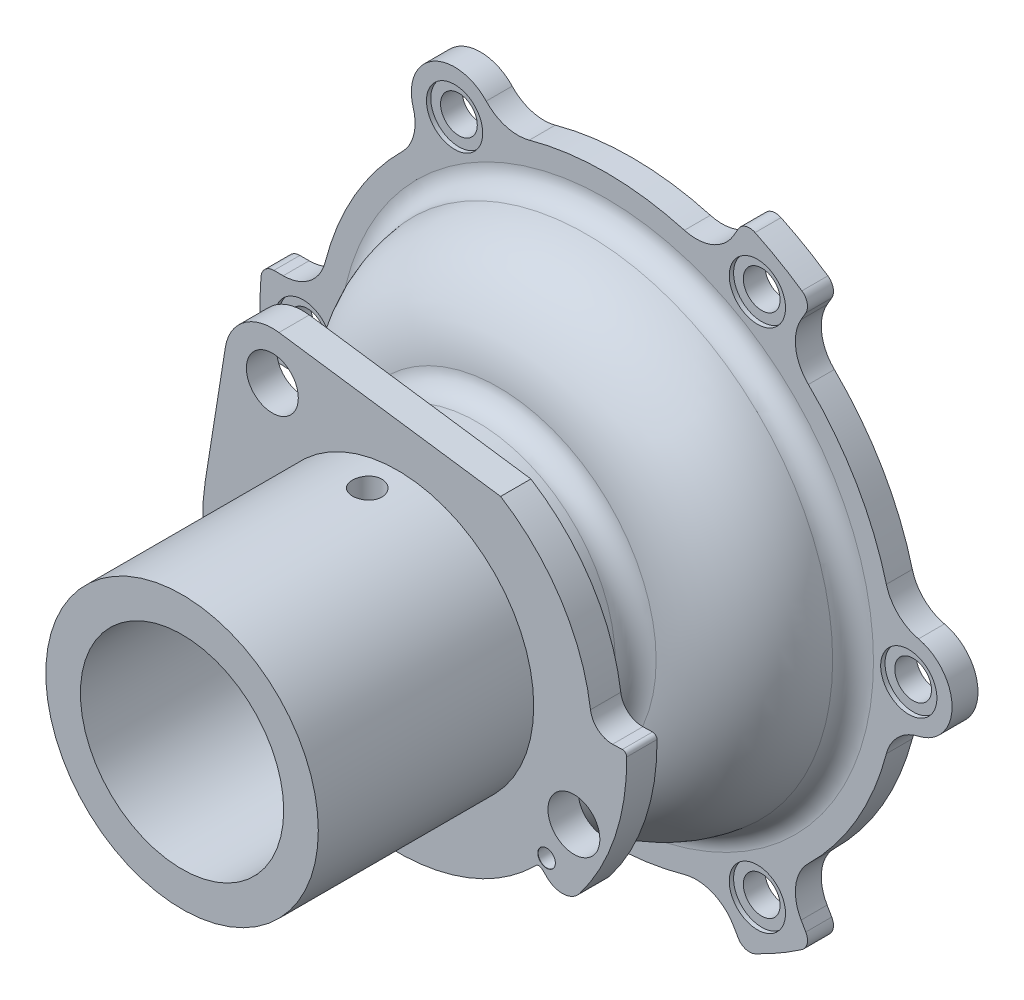
SolidWorks part; units mm, degrees
ref_plane "前视基准面" through (0, 0, 0) normal (0, 0, 1) x (1, 0, 0)
ref_plane "上视基准面" through (0, 0, 0) normal (0, 1, 0) x (1, 0, 0)
ref_plane "右视基准面" through (0, 0, 0) normal (1, 0, 0) x (0, 0, -1)
sketch "草图5" plane through (0, 0, 0) normal (0, 0, 1) x (1, 0, 0)
  circle A0 centre (0, 0) radius 67
  dimension "D1" = 134
extrude "凸台-拉伸1" add sketch "草图5" along normal blind 6
sketch "草图6" plane through (0, 0, 0) normal (0, 0, 1) x (1, 0, 0)
  circle A0 centre (0, 0) radius 31.5
  dimension "D1" = 63
extrude "凸台-拉伸2" add sketch "草图6" along normal blind 104
sketch "草图7" plane through (0, 0, 0) normal (0, 0, 1) x (1, 0, 0)
  line L0 (0, 0) -> (-41.4994, 49.457) construction
  line L1 (0, -57.2) -> (0, 57.2) construction
  line L2 (-39.7878, 36.2068) -> (-44.4369, 7.0969)
  line L3 (-27.3945, 45.3649) -> (23.8436, 38.1639)
  line L4 (34.6624, -32.8255) -> (33.392, -31.6224)
  line L5 (51.9667, 1.57) -> (49.7267, 1.5023)
  line L6 (-8.5155, -48.7492) -> (-6.1102, -44.5832)
  line L7 (57.2, 0) -> (-57.2, 0) construction
  line L8 (0, 0) -> (-47.6758, -82.5768) construction
  line L9 (-34.9226, -34.4878) -> (-32.799, -30.8095)
  arc A0 (-44.4369, 7.0969) -> (-32.799, -30.8095) centre (0, 0) ccw
  arc A1 (-27.3945, 45.3649) -> (-39.7878, 36.2068) centre (-28.9254, 34.472) ccw
  arc A2 (52.9968, 0.5814) -> (42.0693, -32.2363) centre (0, 0) cw
  arc A3 (44.6181, 5.85) -> (23.8436, 38.1639) centre (0, 0) ccw
  arc A4 (49.7267, 1.5023) -> (44.6181, 5.85) centre (49.5757, 6.5) cw
  arc A5 (52.9968, 0.5814) -> (51.9667, 1.57) centre (51.9969, 0.5704) ccw
  arc A6 (42.0693, -32.2363) -> (34.6624, -32.8255) centre (38.1005, -29.1951) cw
  arc A7 (33.392, -31.6224) -> (31.9934, -31.6452) centre (32.7044, -32.3485) ccw
  arc A8 (-33.7792, -40.8407) -> (-14.1837, -51.0669) centre (0, 0) ccw
  arc A9 (-6.1102, -44.5832) -> (31.9934, -31.6452) centre (0, 0) ccw
  arc A10 (-33.7792, -40.8407) -> (-34.9226, -34.4878) centre (-30.5925, -36.9878) cw
  arc A11 (-14.1837, -51.0669) -> (-8.5155, -48.7492) centre (-12.8456, -46.2492) ccw
  point P16 (44.9795, 1.3589)
  dimension "D1" = 90
  dimension "D3" = 22
  dimension "D5" = 5
  dimension "D6" = 1
  dimension "D8" = 5
  dimension "D9" = 1
  dimension "D10" = 53
  dimension "D14" = 53
  dimension "D15" = 5
  dimension "D2" = 40
  dimension "D4" = 42
  dimension "D7" = 1.5
  dimension "D11" = 30
  dimension "D12" = 17
  dimension "D13" = 13
extrude "凸台-拉伸3" add sketch "草图7" against normal blind 7 from offset 54.2
sketch "草图9" plane through (0, 0, 0) normal (0, 0, 1) x (1, 0, 0)
  circle A0 centre (0, 0) radius 32
  dimension "D1" = 64
extrude "凸台-拉伸5" add sketch "草图9" along normal up to surface (47.2 mm away) up to face at (31.5, 0, 47.2)
sketch "草图11" plane through (0, 0, 54.2) normal (0, 0, 1) x (1, 0, 0)
  line L0 (40.7839, -19.0178) -> (0, 0) construction
  line L1 (57.2, 0) -> (-57.2, 0) construction
  line L2 (-19.0178, -40.7839) -> (0, 0) construction
  line L3 (0, -57.2) -> (0, 57.2) construction
  circle A0 centre (-28.9254, 34.472) radius 6
  arc A1 (-27.3945, 45.3649) -> (-39.7878, 36.2068) centre (-28.9254, 34.472) ccw construction
  circle A2 centre (40.7839, -19.0178) radius 6
  arc A3 (44.6181, 5.85) -> (23.8436, 38.1639) centre (0, 0) ccw construction
  circle A4 centre (-19.0178, -40.7839) radius 6
  arc A6 (-6.1102, -44.5832) -> (31.9934, -31.6452) centre (0, 0) ccw construction
  dimension "D1" = 12
  dimension "D2" = 12
  dimension "D4" = 12
  dimension "D3" = 25
  dimension "D5" = 25
extrude "切除-拉伸1" cut sketch "草图11" against normal blind 7
sketch "草图12" plane through (0, 0, 54.2) normal (0, 0, 1) x (1, 0, 0)
  line L0 (0, 0) -> (34.472, -28.9254) construction
  line L1 (0, 0) -> (-29.5781, -36.5259) construction
  line L2 (57.2, 0) -> (-57.2, 0) construction
  line L3 (0, -57.2) -> (0, 57.2) construction
  arc A0 (-6.1102, -44.5832) -> (31.9934, -31.6452) centre (0, 0) ccw construction
  point P11 (34.472, -28.9254)
  point P13 (-29.5781, -36.5259)
  dimension "D1" = 40
  dimension "D2" = 39
  dimension "D3" = 47
hole_wizard "Ø4.0mm 暗销孔1" positions "草图14" profile "草图13" hole size "Ø4.0" standard "GB"
sketch "草图14" plane through (0, 0, 54.2) normal (0, 0, 1) x (1, 0, 0)
  point P0 (21.1612, -36.8231)
  point P1 (34.472, -28.9254)
  point P4 (-29.5781, -36.5259)
sketch "草图13" plane through (-29.5781, -36.5259, 54.2) normal (1, 0, 0) x (0, -1, 0)
  line L0 (0, 0) -> (0, 7)
  line L1 (0, 7) -> (2, 7)
  line L2 (2, 7) -> (2, 0.0433)
  line L3 (2, 0.0433) -> (2.025, 0)
  line L5 (2.025, 0) -> (0, 0)
  line L6 (-2, 0.0433) -> (-2.025, 0) construction
  line L11 (0, -6.35) -> (0, 107.95) construction
  dimension "通孔孔直径" = 4
  dimension "通孔孔深度" = 7
  dimension "近端锥形沉头孔直径" = 4.05
  dimension "近端锥形沉头孔角度" = 60
sketch "草图15" plane through (0, 0, 0) normal (0, 1, 0) x (1, 0, 0)
  line L0 (0, 0) -> (0, -139.9578) construction
  line L1 (-73.7, 0) -> (73.7, 0) construction
  line L2 (-67, -6) -> (67, -6) construction
  line L3 (11.0871, -6) -> (56.9129, -6)
  arc A0 (11.0871, -6) -> (56.9129, -6) centre (34, -8) ccw
  point P7 (34, -31)
  dimension "D1" = 46
  dimension "D2" = 8
  dimension "D3" = 68
revolve "旋转1" add sketch "草图15" angle 360 about L0
fillet "圆角1" radius 5 1 edges at (-56.9129, 0, 6)
fillet "圆角2" radius 5 1 edges at (-32, 0, 30.9129)
sketch "草图17" plane through (0, 0, 0) normal (0, 0, 1) x (1, 0, 0)
  line L0 (57.2, 0) -> (-57.2, 0) construction
  circle A0 centre (70, 0) radius 10
  dimension "D1" = 20
  dimension "D2" = 70
extrude "凸台-拉伸6" add sketch "草图17" along normal blind 6
fillet "圆角3" radius 10 2 edges at (66.35, -9.3101, 3) (66.35, 9.3101, 3)
sketch "草图18" plane through (0, 0, 6) normal (0, 0, 1) x (1, 0, 0)
  point P0 (70, 0)
hole_wizard "孔1" positions "草图18" profile "草图19" legacy end condition through all
sketch "草图19" plane through (70, 0, 6) normal (1, 0, 0) x (0, -1, 0)
  line L0 (0, 0) -> (0, 8.5537)
  line L1 (0, 8.5537) -> (4.25, 6)
  line L2 (4.25, 6) -> (4.25, 1)
  line L3 (4.25, 1) -> (6.5, 1)
  line L4 (6.5, 0) -> (0, 0)
  line L5 (0, -11.3109) -> (0, 121.1557) construction
  line L6 (0, 8.5537) -> (-4.25, 6) construction
  line L7 (6.5, 1) -> (6.5, 0)
  dimension "直径" = 8.5
  dimension "深度" = 6
  dimension "柱坑直径" = 13
  dimension "柱坑深度" = 1
  dimension "导头角度" = 118
pattern_circular "阵列(圆周)1" count 3 over 360 about axis through (0, 0, 0) along (0, 0, 1) of "凸台-拉伸6", "圆角3", "孔1"
sketch "草图20" plane through (0, 0, 0) normal (0, 0, 1) x (1, 0, 0)
  line L0 (57.2, 0) -> (-57.2, 0) construction
  line L1 (0, 0) -> (-94.9525, 0) construction
  line L2 (-79.4906, -9.014) -> (-66.3909, -9.014)
  line L3 (-79.4906, 9.014) -> (-66.3909, 9.014)
  arc A0 (-79.4906, -9.014) -> (-79.4906, 9.014) centre (0, 0) cw
  arc A1 (-66.3909, 9.014) -> (-66.3909, -9.014) centre (0, 0) ccw
  arc A8 (-27.6843, 67.4394) -> (-44.5621, 57.695) centre (-35, 60.6218) ccw construction
  arc A9 (-47.0951, 47.6555) -> (-47.0951, -47.6555) centre (0, 0) ccw construction
  dimension "D1" = 18.028
extrude "凸台-拉伸7" add sketch "草图20" along normal blind 6
fillet "圆角4" radius 3 2 edges at (-79.4906, 9.014, 3) (-79.4906, -9.014, 3)
fillet "圆角5" radius 10 2 edges at (-66.3909, -9.014, 3) (-66.3909, 9.014, 3)
pattern_circular "阵列(圆周)2" count 3 over 360 about axis through (0, 0, 0) along (0, 0, 1) of "凸台-拉伸7", "圆角4", "圆角5"
pattern_circular "阵列(圆周)3" count 6 over 360 about axis through (0, 0, 0) along (0, 0, 1) of "孔1"
sketch "草图23" plane through (0, 0, 0) normal (0, 0, -1) x (-1, 0, 0)
  circle A0 centre (0, 0) radius 50
  dimension "D1" = 100
extrude "切除-拉伸2" cut sketch "草图23" against normal blind 6
sketch "草图24" plane through (0, 0, 0) normal (1, 0, 0) x (0, 0, -1)
  line L0 (-25, -34) -> (-25, 0)
  line L1 (57.2, 0) -> (-57.2, 0) construction
  line L2 (-25, 0) -> (0, 0)
  line L3 (0, 0) -> (0, -19)
  line L4 (0, 79.736) -> (0, -79.736) construction
  line L5 (0, 0) -> (18.6041, 0) construction
  arc A0 (-25, -34) -> (0, -19) centre (-8, -34) ccw
  arc A1 (-30.8676, -36.4643) -> (-10.4643, -56.8676) centre (-8, -34) ccw construction
  dimension "D1" = 34
revolve "切除-旋转1" cut sketch "草图24" angle 360 about L5
sketch "草图25" plane through (0, 0, 0) normal (0, 0, -1) x (-1, 0, 0)
  circle A0 centre (0, 0) radius 25
  dimension "D1" = 50
extrude "切除-拉伸3" cut sketch "草图25" against normal blind 31
fillet "圆角6" radius 5 1 edges at (-25, 0, 31)
fillet "圆角7" radius 11 1 edges at (25, 0, 25)
sketch "草图26" plane through (0, 0, 31) normal (0, 0, -1) x (-1, 0, 0)
  circle A0 centre (0, 0) radius 12.5
  dimension "D1" = 25
extrude "切除-拉伸4" cut sketch "草图26" against normal through all
sketch "草图28" plane through (0, 0, 0) normal (0, 1, 0) x (1, 0, 0)
  line L0 (0, -35) -> (12.5, -35)
  line L1 (0, -57.2) -> (0, 57.2) construction
  line L2 (12.5, -35) -> (17.5, -36)
  line L3 (17.5, -36) -> (17.5, -40)
  line L4 (17.5, -40) -> (12.5, -41)
  line L5 (12.5, -41) -> (0, -41)
  line L6 (0, -35) -> (0, -41) construction
  line L7 (12.5, -31) -> (-12.5, -31) construction
  line L8 (0, -35) -> (0, -41)
  dimension "D1" = 35
  dimension "D2" = 25
  dimension "D3" = 25
  dimension "D4" = 1
  dimension "D5" = 4
  dimension "D6" = 4
revolve "切除-旋转2" cut sketch "草图28" angle 360 about L6
sketch "草图29" plane through (0, 0, 104) normal (0, 0, 1) x (1, 0, 0)
  circle A0 centre (0, 0) radius 20
  dimension "D1" = 40
extrude "切除-拉伸5" cut sketch "草图29" against normal offset from surface (59.8 mm away) 3 up to face at (36.472, -28.9254, 47.2) offset beyond the face yes
sketch "草图30" plane through (0, 0, 104) normal (0, 0, 1) x (1, 0, 0)
  circle A0 centre (0, 0) radius 23.5
  dimension "D1" = 47
extrude "切除-拉伸6" cut sketch "草图30" against normal up to surface (56.8 mm away) up to face at (36.472, -28.9254, 47.2)
sketch "草图31" plane through (0, 0, 47.2) normal (0, 0, 1) x (1, 0, 0)
  circle A0 centre (0, 0) radius 25
  dimension "D1" = 50
extrude "切除-拉伸7" cut sketch "草图31" against normal blind 2
sketch "草图35" plane through (0, 0, 0) normal (0, 1, 0) x (1, 0, 0)
  line L0 (0, -57.2) -> (0, 57.2) construction
  line L1 (-31.5, -54.2) -> (31.5, -54.2) construction
  point P0 (0, -61.2)
  dimension "D1" = 7
hole_wizard "M8 螺纹孔1" positions "草图35" profile "草图36" tap size "M8" standard "GB"
sketch "草图36" plane through (0, 0, 61.2) normal (1, 0, 0) x (0, 0, -1)
  line L0 (0, 0) -> (0, 72.4873)
  line L1 (0, 72.4873) -> (3.4, 72.4873)
  line L2 (3.4, 72.4873) -> (3.4, 0.625)
  line L3 (3.4, 0.625) -> (4.025, 0)
  line L5 (4.025, 0) -> (0, 0)
  line L6 (-3.4, 0.625) -> (-4.025, 0) construction
  line L11 (0, -6.35) -> (0, 107.95) construction
  dimension "通孔螺纹孔钻头直径" = 6.8
  dimension "通孔螺纹孔钻头深度" = 72.4873
  dimension "近端锥形沉头孔直径" = 8.05
  dimension "近端锥形沉头孔角度" = 90
cosmetic thread "孔螺纹线1" parameters "D2"=8
equation "\"D14@草图7\"=\"D10@草图7\""
